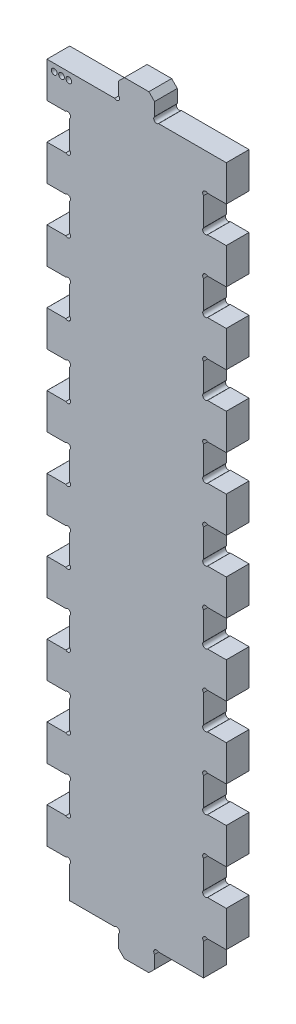
SolidWorks part; units mm, degrees
material "PVC Rigid"
ref_plane "Front Plane" through (0, 0, 0) normal (0, 0, 1) x (1, 0, 0)
ref_plane "Top Plane" through (0, 0, 0) normal (0, 1, 0) x (1, 0, 0)
ref_plane "Right Plane" through (0, 0, 0) normal (1, 0, 0) x (0, 0, -1)
sketch "Model" [suppressed]
  dimension "D3" = 0.7937
  dimension "D1" = 10
  dimension "D2" = 10
sketch "Sketch1" plane through (0, 0, 0) normal (0, 0, 1) x (1, 0, 0)
  line L1 (0, 0) -> (50, 0)
  line L2 (0, 0) -> (0, 200.0001)
  line L3 (0, 200.0001) -> (50, 200.0001)
  line L4 (50, 0) -> (50, 200.0001)
  dimension "D1" = 200.0001
  dimension "D2" = 50
extrude "Boss-Extrude1" add sketch "Sketch1" along normal blind 6.35
sketch "Sketch2" plane through (0, 0, 0) normal (0, 0, 1) x (1, 0, 0)
  line L0 (0, 100.0001) -> (50, 100.0001) construction
  line L1 (50, 200.0001) -> (0, 200.0001) construction
  line L2 (25, 200.0001) -> (25, 203.1751) construction
  line L3 (20, 206.3501) -> (30, 206.3501)
  line L4 (20, 206.3501) -> (20, 200.0001)
  line L5 (20, 200.0001) -> (30, 200.0001)
  line L6 (30, 206.3501) -> (30, 200.0001)
  line L7 (20, 206.3501) -> (30, 200.0001) construction
  line L8 (20, 200.0001) -> (30, 206.3501) construction
  line L9 (0, 200.0001) -> (0, 0) construction
  line L10 (50, 0) -> (50, 200.0001) construction
  line L11 (20, 0) -> (30, -6.35) construction
  line L12 (20, -6.35) -> (30, 0) construction
  line L13 (25, 0) -> (25, -3.175) construction
  line L14 (30, -6.35) -> (30, 0)
  line L15 (20, 0) -> (30, 0)
  line L16 (20, -6.35) -> (20, 0)
  line L17 (20, -6.35) -> (30, -6.35)
  dimension "D1" = 6.35
  dimension "D2" = 10
extrude "Boss-Extrude2" add sketch "Sketch2" along normal blind 6.35
sketch "Sketch3" plane through (0, 0, 6.35) normal (0, 0, 1) x (1, 0, 0)
  line L0 (25, 206.3501) -> (25, -6.35) construction
  line L1 (30, 206.3501) -> (20, 206.3501) construction
  line L2 (20, -6.35) -> (30, -6.35) construction
  line L3 (6.35, 200.0001) -> (6.35, 0) construction
  line L4 (20, 200.0001) -> (0, 200.0001) construction
  line L5 (0, 0) -> (20, 0) construction
  line L6 (0, 200.0001) -> (0, 0) construction
  line L7 (6.35, 0) -> (0, 0)
  line L8 (6.35, 0) -> (6.35, 10)
  line L9 (6.35, 10) -> (0, 10)
  line L10 (0, 0) -> (0, 10)
  line L11 (50, 0) -> (50, 10)
  line L12 (43.65, 10) -> (50, 10)
  line L13 (43.65, 0) -> (43.65, 10)
  line L14 (43.65, 0) -> (50, 0)
  dimension "D1" = 6.35
  dimension "D2" = 10
extrude "Cut-Extrude1" cut sketch "Sketch3" against normal blind 6.35
pattern_linear "LPattern2" count 10 spacing 20 along (0, 1, 0) of "Cut-Extrude1"
sketch "Sketch4" plane through (0, 0, 6.35) normal (0, 0, 1) x (1, 0, 0)
  line L0 (0, 10) -> (6.35, 0) construction
  line L1 (6.35, 10) -> (5.2275, 10) construction
  line L2 (0.5613, 0.5613) -> (5.7887, 0.5613) construction
  line L3 (0.5613, 0.5613) -> (0.5613, 9.4387) construction
  line L4 (0.5613, 9.4387) -> (5.7887, 9.4387) construction
  line L5 (5.7887, 0.5613) -> (5.7887, 9.4387) construction
  line L6 (0.5613, 0.5613) -> (5.7887, 9.4387) construction
  line L7 (0.5613, 9.4387) -> (5.7887, 0.5613) construction
  line L8 (6.35, 10) -> (0, 10) construction
  line L9 (6.35, 10) -> (6.35, 8.8775) construction
  line L10 (6.35, 0) -> (6.35, 10) construction
  line L11 (25, 206.3501) -> (25, -6.35) construction
  line L12 (30, 206.3501) -> (20, 206.3501) construction
  line L13 (20, -6.35) -> (30, -6.35) construction
  line L14 (44.2113, 9.4387) -> (44.2113, 20.5613) construction
  line L15 (43.65, 10) -> (43.65, 8.8775) construction
  line L16 (49.4387, 9.4387) -> (44.2113, 0.5613) construction
  line L17 (49.4387, 0.5613) -> (44.2113, 9.4387) construction
  line L18 (44.2113, 0.5613) -> (44.2113, 9.4387) construction
  line L19 (49.4387, 9.4387) -> (44.2113, 9.4387) construction
  line L20 (49.4387, 0.5613) -> (49.4387, 9.4387) construction
  line L21 (49.4387, 0.5613) -> (44.2113, 0.5613) construction
  line L22 (43.65, 10) -> (44.7725, 10) construction
  line L23 (5.7887, 9.4387) -> (5.7887, 20.5613) construction
  line L24 (50, 10) -> (43.65, 0) construction
  circle A0 centre (5.7887, 9.4387) radius 0.7938
  circle A4 centre (5.7887, 20.5613) radius 0.7938
  circle A7 centre (44.2113, 20.5613) radius 0.7937
  circle A8 centre (44.2113, 9.4387) radius 0.7937
  point P4 (3.175, 5)
  point P40 (46.825, 5)
  dimension "D1" = 1.5875
extrude "Cut-Extrude3" cut sketch "Sketch4" against normal blind 6.35
pattern_linear "LPattern3" count 9 spacing 20 along (0, 1, 0) of "Cut-Extrude3"
sketch "Sketch8" [suppressed] plane through (0, 0, 6.35) normal (0, 0, 1) x (1, 0, 0)
  line L0 (6.35, 200.0001) -> (6.35, 0) construction
  line L1 (20, 200.0001) -> (0, 200.0001) construction
  line L2 (0, 0) -> (20, 0) construction
  line L3 (0, 200.0001) -> (0, 0) construction
  line L4 (43.65, 200.0001) -> (43.65, 0) construction
  line L5 (0, 0) -> (6.35, 0)
  line L6 (0, 0) -> (0, 10)
  line L7 (0, 10) -> (6.35, 10)
  line L8 (6.35, 0) -> (6.35, 10)
  line L9 (50, 200.0001) -> (30, 200.0001) construction
  line L10 (30, 0) -> (50, 0) construction
  line L11 (50, 0) -> (50, 200.0001) construction
  line L12 (43.65, 10) -> (50, 10)
  line L13 (43.65, 10) -> (43.65, 20)
  line L14 (43.65, 20) -> (50, 20)
  line L15 (50, 10) -> (50, 20)
  dimension "D1" = 6.35
  dimension "D2" = 10
  dimension "D3" = 10
  dimension "D4" = 6.35
  dimension "D5" = 10
extrude "Cut-Extrude6" [suppressed] cut sketch "Sketch8" against normal through all
pattern_linear "LPattern4" [suppressed] count 10 spacing 20 of bodies 116
sketch "Sketch9" [suppressed] plane through (0, 0, 6.35) normal (0, 0, 1) x (1, 0, 0)
  line L0 (0, 30) -> (6.35, 20) construction
  line L1 (6.35, 30) -> (5.2275, 30) construction
  line L2 (0.5613, 20.5613) -> (5.7887, 20.5613) construction
  line L3 (0.5613, 20.5613) -> (0.5613, 29.4388) construction
  line L4 (0.5613, 29.4388) -> (5.7887, 29.4388) construction
  line L5 (5.7887, 20.5613) -> (5.7887, 29.4388) construction
  line L6 (0.5613, 20.5613) -> (5.7887, 29.4388) construction
  line L7 (0.5613, 29.4388) -> (5.7887, 20.5613) construction
  line L8 (6.35, 30) -> (0, 30) construction
  line L9 (6.35, 30) -> (6.35, 28.8775) construction
  line L10 (6.35, 20) -> (6.35, 30) construction
  line L11 (43.65, 20) -> (50, 10) construction
  line L12 (43.65, 20) -> (44.7725, 20) construction
  line L13 (44.2113, 10.5613) -> (49.4387, 10.5613) construction
  line L14 (44.2113, 10.5613) -> (44.2113, 19.4387) construction
  line L15 (44.2113, 19.4387) -> (49.4387, 19.4387) construction
  line L16 (49.4387, 10.5613) -> (49.4387, 19.4387) construction
  line L17 (44.2113, 10.5613) -> (49.4387, 19.4387) construction
  line L18 (44.2113, 19.4387) -> (49.4387, 10.5613) construction
  line L19 (50, 20) -> (43.65, 20) construction
  line L20 (43.65, 20) -> (43.65, 18.8775) construction
  line L21 (43.65, 20) -> (43.65, 10) construction
  line L22 (50, 20) -> (50, 30) construction
  circle A0 centre (5.7887, 29.4388) radius 0.7938
  circle A1 centre (5.7887, 20.5613) radius 0.7938
  circle A2 centre (44.2113, 19.4387) radius 0.7937
  circle A3 centre (44.2113, 10.5613) radius 0.7937
  point P4 (3.175, 25)
  point P23 (46.825, 15)
  dimension "D1" = 1.5875
  dimension "D2" = 10
extrude "Cut-Extrude7" [suppressed] cut sketch "Sketch9" against normal through all
pattern_linear "LPattern5" [suppressed] count 9 spacing 20 of bodies 118
sketch "Sketch10" [suppressed] plane through (0, 0, 6.35) normal (0, 0, 1) x (1, 0, 0)
  line L0 (0, 10) -> (6.35, 0) construction
  line L1 (5.2275, 10) -> (6.35, 10) construction
  line L2 (0.5613, 0.5613) -> (5.7887, 0.5613) construction
  line L3 (0.5613, 0.5613) -> (0.5613, 9.4387) construction
  line L4 (0.5613, 9.4387) -> (5.7887, 9.4387) construction
  line L5 (5.7887, 0.5613) -> (5.7887, 9.4387) construction
  line L6 (0.5613, 0.5613) -> (5.7887, 9.4387) construction
  line L7 (0.5613, 9.4387) -> (5.7887, 0.5613) construction
  line L8 (6.35, 10) -> (0, 10) construction
  line L9 (6.35, 10) -> (6.35, 8.8775) construction
  line L10 (6.35, 0) -> (6.35, 10) construction
  line L11 (6.35, 5) -> (3.175, 5) construction
  line L12 (0, 200.0001) -> (50, 0) construction
  line L13 (43.65, 200.0001) -> (50, 190.0001) construction
  line L14 (44.7725, 190.0001) -> (43.65, 190.0001) construction
  line L15 (44.2113, 190.5614) -> (49.4387, 190.5614) construction
  line L16 (44.2113, 190.5614) -> (44.2113, 199.4388) construction
  line L17 (44.2113, 199.4388) -> (49.4387, 199.4388) construction
  line L18 (49.4387, 190.5614) -> (49.4387, 199.4388) construction
  line L19 (44.2113, 190.5614) -> (49.4387, 199.4388) construction
  line L20 (44.2113, 199.4388) -> (49.4387, 190.5614) construction
  line L21 (43.65, 190.0001) -> (50, 190.0001) construction
  line L22 (43.65, 190.0001) -> (43.65, 191.1226) construction
  line L23 (43.65, 200.0001) -> (43.65, 190.0001) construction
  circle A0 centre (5.7887, 9.4387) radius 0.7938
  circle A2 centre (44.2113, 190.5614) radius 0.7937
  point P4 (3.175, 5)
  point P28 (46.825, 195.0001)
  dimension "D1" = 1.5875
  dimension "D2" = 1.5875
extrude "Cut-Extrude8" [suppressed] cut sketch "Sketch10" against normal through all
chamfer "Chamfer1" distance 1.5875 angle 45 4 edges at (30, -6.35, 3.175) (20, -6.35, 3.175) (20, 206.3501, 3.175) (30, 206.3501, 3.175)
sketch "Sketch5" plane through (0, 0, 6.35) normal (0, 0, 1) x (1, 0, 0)
  line L0 (6.35, 180.0001) -> (0, 190.0001) construction
  line L1 (6.35, 190.0001) -> (5.2275, 190.0001) construction
  line L2 (0.5613, 180.5614) -> (5.7887, 180.5614) construction
  line L3 (0.5613, 180.5614) -> (0.5613, 189.4388) construction
  line L4 (0.5613, 189.4388) -> (5.7887, 189.4388) construction
  line L5 (5.7887, 180.5614) -> (5.7887, 189.4388) construction
  line L6 (0.5613, 180.5614) -> (5.7887, 189.4388) construction
  line L7 (0.5613, 189.4388) -> (5.7887, 180.5614) construction
  line L8 (6.35, 190.0001) -> (0, 190.0001) construction
  line L9 (6.35, 190.0001) -> (6.35, 188.8776) construction
  line L10 (6.35, 181.1226) -> (6.35, 190.0001) construction
  line L15 (25, 206.3501) -> (25, -6.35) construction
  line L16 (28.4125, 206.3501) -> (21.5875, 206.3501) construction
  line L17 (21.5875, -6.35) -> (28.4125, -6.35) construction
  line L20 (43.65, 190.0001) -> (43.65, 188.8776) construction
  line L21 (49.4387, 189.4388) -> (44.2113, 180.5614) construction
  line L22 (49.4387, 180.5614) -> (44.2113, 189.4388) construction
  line L23 (44.2113, 180.5614) -> (44.2113, 189.4388) construction
  line L24 (49.4387, 189.4388) -> (44.2113, 189.4388) construction
  line L25 (49.4387, 180.5614) -> (49.4387, 189.4388) construction
  line L26 (49.4387, 180.5614) -> (44.2113, 180.5614) construction
  line L27 (43.65, 190.0001) -> (44.7725, 190.0001) construction
  line L28 (43.65, 180.0001) -> (50, 190.0001) construction
  line L29 (50, 100.0001) -> (0, 100.0001) construction
  arc A0 (5.2275, 180.0001) -> (6.35, 181.1226) centre (5.7887, 180.5614) ccw construction
  circle A1 centre (5.7887, 189.4388) radius 0.7938
  circle A4 centre (44.2113, 189.4388) radius 0.7937
  point P6 (3.175, 185.0001)
  point P51 (46.825, 185.0001)
  point P56 (25, 100.0001)
  dimension "D1" = 1.5875
extrude "Cut-Extrude4" cut sketch "Sketch5" against normal blind 6.35
sketch "Sketch11" plane through (0, 0, 0) normal (0, 0, 1) x (1, 0, 0)
  line L0 (28.4125, 206.3501) -> (21.5875, 206.3501) construction
  line L11 (20, 201.1226) -> (20, 200.0001) construction
  line L13 (20, 200.0001) -> (18.8775, 200.0001) construction
  line L15 (25, 206.3501) -> (25, -6.35) construction
  line L18 (30, 200.0001) -> (31.1225, 200.0001) construction
  line L19 (30, 201.1226) -> (30, 200.0001) construction
  line L29 (50, 100.0001) -> (0, 100.0001) construction
  circle A2 centre (19.4387, 200.5614) radius 0.7937
  circle A3 centre (30.5613, 200.5614) radius 0.7937
  circle A5 centre (19.4387, -0.5613) radius 0.7937
  circle A6 centre (30.5613, -0.5613) radius 0.7937
  point P56 (25, 100.0001)
  dimension "D1" = 1.5875
  dimension "D2" = 19.4387
  dimension "D3" = 100.0001
  dimension "D4" = 200.0001
extrude "Cut-Extrude10" cut sketch "Sketch11" along normal through all
sketch "Sketch6" plane through (0, 0, 6.35) normal (0, 0, 1) x (1, 0, 0)
  line L0 (6.604, 2.032) -> (43.65, 2.032) construction
  line L1 (43.65, 8.8775) -> (43.65, 0) construction
  line L2 (6.35, 0) -> (18.8775, 0) construction
  line L4 (0, 20) -> (0, 10) construction
  text T0 "COR" font "Consolas" height 3.5
  dimension "D1" = 2.032
  dimension "D2" = 6.604
extrude "Cut-Extrude5" [suppressed] cut sketch "Sketch6" against normal blind 2.54
sketch "Sketch12" [suppressed]
  dimension "D1" = 2.032
  dimension "D2" = 6.604
extrude "Cut-Extrude11" [suppressed] cut sketch "Sketch12" against normal blind 2.54
sketch "Sketch13" plane through (0, 0, 6.35) normal (0, 0, 1) x (1, 0, 0)
  line L0 (0, 10) -> (6.35, 0) construction
  line L1 (5.2275, 10) -> (0, 10) construction
  line L2 (6.337, -0.0127) -> (0.013, -0.0127)
  line L3 (6.337, -0.0127) -> (6.337, 10.0127)
  line L4 (6.337, 10.0127) -> (0.013, 10.0127)
  line L5 (0.013, -0.0127) -> (0.013, 10.0127)
  line L6 (6.337, -0.0127) -> (0.013, 10.0127) construction
  line L7 (6.337, 10.0127) -> (0.013, -0.0127) construction
  line L8 (25, 206.3501) -> (25, -6.35) construction
  line L9 (28.4125, 206.3501) -> (21.5875, 206.3501) construction
  line L10 (21.5875, -6.35) -> (28.4125, -6.35) construction
  line L11 (43.663, 10.0127) -> (49.987, -0.0127) construction
  line L12 (43.663, -0.0127) -> (49.987, 10.0127) construction
  line L13 (50, 10) -> (43.65, 0) construction
  line L14 (49.987, -0.0127) -> (49.987, 10.0127)
  line L15 (43.663, 10.0127) -> (49.987, 10.0127)
  line L16 (43.663, -0.0127) -> (43.663, 10.0127)
  line L17 (43.663, -0.0127) -> (49.987, -0.0127)
  arc A0 (6.35, 8.8775) -> (5.2275, 10) centre (5.7887, 9.4387) ccw construction
  point P4 (3.175, 5)
  point P26 (46.825, 5)
  dimension "D1" = 0.0127
extrude "Cut-Extrude12" cut sketch "Sketch13" against normal through all
pattern_linear "LPattern6" count 10 spacing 20 along (0, 1, 0) of "Cut-Extrude12"
sketch "Sketch14" [suppressed] plane through (0, 0, 6.35) normal (0, 0, 1) x (1, 0, 0)
  line L0 (0, 10) -> (6.35, 0) construction
  line L1 (5.2275, 10) -> (0, 10) construction
  line L2 (0.013, -0.0127) -> (6.337, -0.0127)
  line L3 (0.013, -0.0127) -> (0.013, 10.0127)
  line L4 (0.013, 10.0127) -> (6.337, 10.0127)
  line L5 (6.337, -0.0127) -> (6.337, 10.0127)
  line L6 (0.013, -0.0127) -> (6.337, 10.0127) construction
  line L7 (0.013, 10.0127) -> (6.337, -0.0127) construction
  line L8 (43.65, 20) -> (50, 10) construction
  line L9 (50, 20) -> (44.7725, 20) construction
  line L10 (43.663, 9.9873) -> (49.987, 9.9873)
  line L11 (43.663, 9.9873) -> (43.663, 20.0127)
  line L12 (43.663, 20.0127) -> (49.987, 20.0127)
  line L13 (49.987, 9.9873) -> (49.987, 20.0127)
  line L14 (43.663, 9.9873) -> (49.987, 20.0127) construction
  line L15 (43.663, 20.0127) -> (49.987, 9.9873) construction
  arc A0 (6.35, 8.8775) -> (5.2275, 10) centre (5.7887, 9.4387) ccw construction
  arc A1 (44.7725, 20) -> (43.65, 18.8775) centre (44.2113, 19.4387) ccw construction
  point P4 (3.175, 5)
  point P9 (46.825, 15)
  dimension "D1" = 0.0127
  dimension "D2" = 0.0127
extrude "Cut-Extrude13" [suppressed] cut sketch "Sketch14" against normal through all
pattern_linear "LPattern7" [suppressed] count 10 spacing 20 of bodies 125
sketch "Sketch15" plane through (0, 0, 6.35) normal (0, 0, 1) x (1, 0, 0)
  line L1 (0, 200.0001) -> (2.032, 200.0001) construction
  line L2 (0, 200.0001) -> (0, 197.9681) construction
  line L3 (0, 197.9681) -> (2.032, 197.9681) construction
  line L4 (2.032, 200.0001) -> (2.032, 197.9681) construction
  circle A0 centre (2.032, 197.9681) radius 0.7938
  dimension "D2" = 1.5875
  dimension "D1" = 2.032
extrude "Cut-Extrude14" cut sketch "Sketch15" against normal blind 3.175
pattern_linear "LPattern8" count 3 spacing 2.032 along (1, 0, 0) of "Cut-Extrude14"
equation "\"tHeight\"=0.25"
equation "\"D1@Sketch2\"=\"tHeight\""
equation "\"tWidth\"=0.393701"
equation "\"D2@Sketch2\"=\"tWidth\""
equation "\"D1@Sketch1\"=\"tWidth\"*20"
equation "\"D1@Sketch3\"=\"tHeight\""
equation "\"D2@Sketch3\"=\"tWidth\""
equation "\"D3@LPattern2\"=\"tWidth\"*2"
equation "\"D3@LPattern3\"=\"tWidth\"*2"
equation "\"D1@Sketch8\"=\"tHeight\""
equation "\"D2@Sketch8\"=\"tWidth\""
equation "\"D3@Sketch8\"=\"tWidth\""
equation "\"D4@Sketch8\"=\"tHeight\""
equation "\"D5@Sketch8\"=\"tWidth\""
equation "\"D3@LPattern4\"=\"tWidth\"*2"
equation "\"D3@LPattern5\"=\"tWidth\"*2"
equation "\"D2@Sketch9\"=\"tWidth\""
equation "\"tol\"=0.0005"
equation "\"D1@Sketch13\"=\"tol\""
equation "\"D3@LPattern6\"=\"tWidth\"*2"
equation "\"D1@Sketch14\"=\"tol\""
equation "\"D2@Sketch14\"=\"tol\""
equation "\"version\"= 3"
equation "\"D1@LPattern8\"=\"version\""
